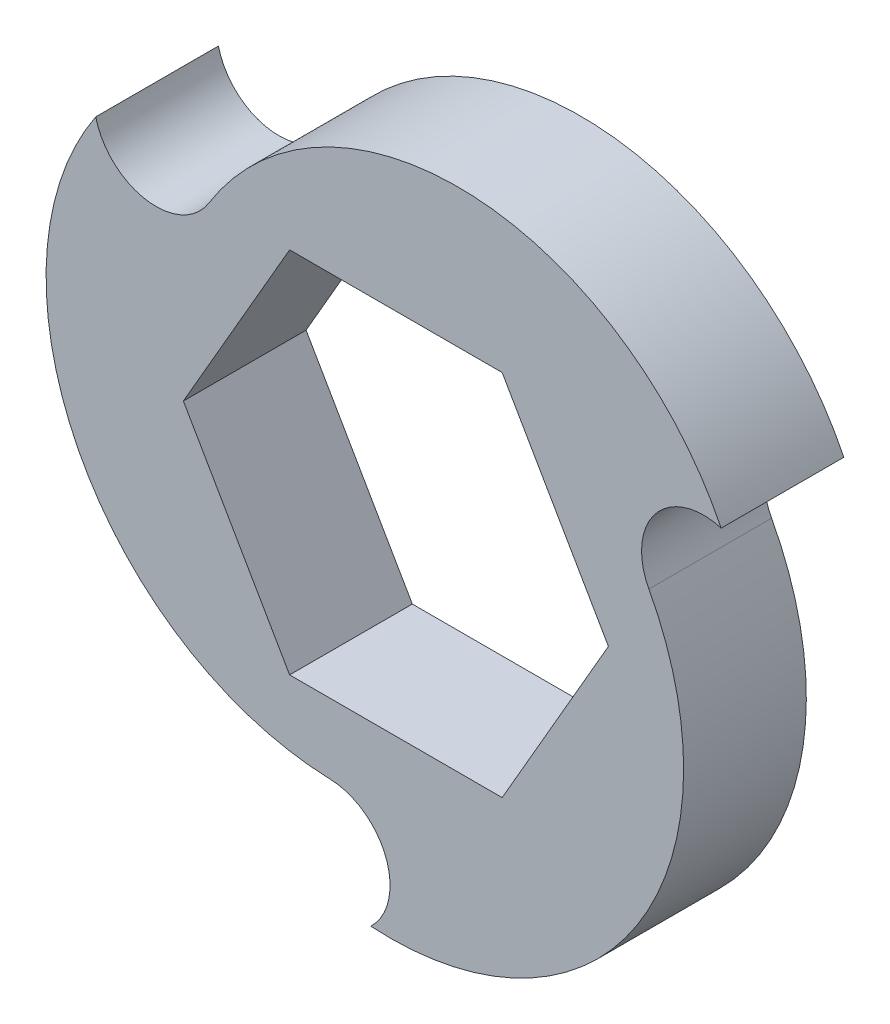
SolidWorks part; units mm, degrees
ref_plane "Front Plane" through (0, 0, 0) normal (0, 0, 1) x (1, 0, 0)
ref_plane "Top Plane" through (0, 0, 0) normal (0, 1, 0) x (1, 0, 0)
ref_plane "Right Plane" through (0, 0, 0) normal (1, 0, 0) x (0, 0, -1)
sketch "Sketch1" plane through (0, 0, 0) normal (0, 0, 1) x (1, 0, 0)
  line L6 (0, 0) -> (66.1503, 0) construction
  line L7 (8.6603, 0) -> (4.3301, 7.5)
  line L8 (4.3301, 7.5) -> (-4.3301, 7.5)
  line L9 (-4.3301, 7.5) -> (-8.6603, 0)
  line L10 (-8.6603, 0) -> (-4.3301, -7.5)
  line L11 (-4.3301, -7.5) -> (4.3301, -7.5)
  line L12 (4.3301, -7.5) -> (8.6603, 0)
  line L13 (0, 0) -> (-15.3926, 15.1529) construction
  line L14 (0, 0) -> (21.3672, 5.9055) construction
  circle A0 centre (0, 0) radius 14.75 construction
  arc A1 (271.8524, 134.8606) -> (128.8311, 107.2295) centre (210.3708, 69.1338) ccw construction
  arc A2 (101.7797, 101.1876) -> (128.8311, 107.2295) centre (112.9762, 114.637) ccw construction
  arc A3 (271.8524, 134.8606) -> (263.5592, 108.4124) centre (277.9018, 118.4394) ccw construction
  arc A4 (215.9777, -29.2632) -> (197.2195, -8.857) centre (198.7319, -26.2915) ccw construction
  arc A5 (215.9777, -29.2632) -> (263.5592, 108.4124) centre (189.7975, 56.8448) ccw construction
  arc A6 (101.7797, 101.1876) -> (197.2195, -8.857) centre (189.4416, 80.8063) ccw construction
  circle A7 centre (0, 0) radius 7.5 construction
  arc A8 (-7.6229, 7.5042) -> (13.2544, 6.4718) centre (2.5296, 1.2012) cw
  arc A9 (13.2544, 6.4718) -> (10.3103, 2.8496) centre (12.541, 4.044) ccw
  arc A10 (10.3103, 2.8496) -> (-1.0225, -14.7145) centre (-0.2245, -2.7913) cw
  arc A11 (-1.0225, -14.7145) -> (-2.6873, -10.3537) centre (-2.7683, -12.8828) ccw
  arc A12 (-2.6873, -10.3537) -> (-12.2319, 8.2428) centre (-2.3051, 1.5901) cw
  arc A13 (-12.2319, 8.2428) -> (-7.6229, 7.5042) centre (-9.7727, 8.8388) ccw
  point P3 (0, 0)
  point P4 (0, 0)
  point P5 (0, 0)
  point P9 (95.6823, 117.3148)
  point P11 (128.6223, 31.4883)
  point P12 (212.2895, -27.5921)
  point P39 (-12.0144, 9.793)
  point P40 (-12.7206, 8.8565)
  point P44 (-12.9599, 8.5023)
  point P45 (-12.5165, 9.1705)
  point P46 (-12.8539, 8.6619)
  dimension "D1" = 29.5
  dimension "D2" = 120
  dimension "D3" = 15
  dimension "D4" = 3
extrude "Boss-Extrude1" add sketch "Sketch1" along normal blind 5
